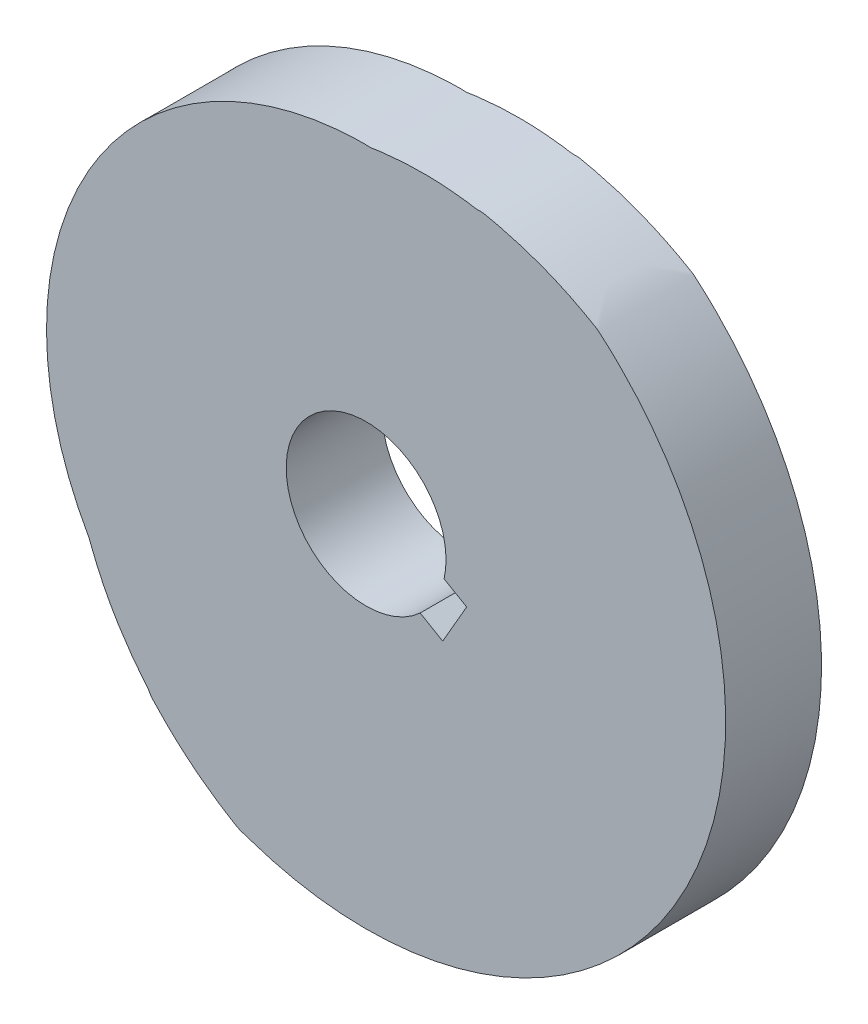
SolidWorks part; units mm, degrees
material "45"
ref_plane "前视基准面" through (0, 0, 0) normal (0, 0, 1) x (1, 0, 0)
ref_plane "上视基准面" through (0, 0, 0) normal (0, 1, 0) x (1, 0, 0)
ref_plane "右视基准面" through (0, 0, 0) normal (1, 0, 0) x (0, 0, -1)
ref_axis "基准轴1" through (0, 0, -88.99) along (0, 0, 1)
sketch "草图1" plane through (0, 0, 0) normal (0, 0, 1) x (1, 0, 0)
  arc A0 (28.9254, 34.472) -> (-15.3909, -42.2862) centre (0, 0) cw construction
  arc A1 (-34.641, -20) -> (0, 40) centre (0, 0) cw construction
  spline S0 degree 3 poles (0, 40) (0.4748, 39.9243) (1.1694, 40.08) (2.1071, 40.1955) (2.8169, 40.2793) (3.5303, 40.348) (4.247, 40.4047) (4.9668, 40.4484) (5.6893, 40.4794) (6.4145, 40.4974) (7.142, 40.5024) (7.8716, 40.4943) (8.6031, 40.473) (9.3363, 40.4385) (10.0709, 40.3908) (10.8066, 40.3293) (11.5433, 40.2558) (12.2803, 40.1639) (13.0194, 40.0767) (13.7627, 39.9054) (14.5314, 39.9845) (15.2755, 39.7844) (16.0159, 39.6423) (16.7537, 39.4678) (17.491, 39.2847) (18.2267, 39.0865) (18.9609, 38.8748) (19.6932, 38.6494) (20.4234, 38.4102) (21.1513, 38.1572) (21.8765, 37.8905) (22.5988, 37.6101) (23.318, 37.316) (24.0338, 37.0082) (24.7459, 36.6867) (25.4541, 36.3517) (26.1581, 36.003) (26.8577, 35.6409) (27.7855, 35.1393) (28.472, 34.744) (28.9254, 34.472) knots 0 0 0 0 0.046842 0.070536 0.094303 0.11814 0.142049 0.16603 0.190082 0.214205 0.2384 0.262667 0.287004 0.311414 0.335895 0.360447 0.385071 0.409766 0.434533 0.459372 0.485336 0.510389 0.535514 0.56071 0.585978 0.611317 0.636728 0.662211 0.687765 0.713391 0.739088 0.764857 0.790697 0.816609 0.842593 0.868649 0.894776 0.920974 0.947244 1 1 1 1 construction
  spline S1 degree 3 poles (-15.3909, -42.2862) (-15.9186, -42.1748) (-16.5847, -41.7396) (-17.4865, -41.1963) (-18.1511, -40.769) (-18.8073, -40.3331) (-19.4535, -39.8863) (-20.0899, -39.4294) (-20.7163, -38.9623) (-21.3325, -38.4855) (-21.9384, -37.9991) (-22.5339, -37.5033) (-23.1187, -36.9983) (-23.6928, -36.4844) (-24.256, -35.9616) (-24.8084, -35.4306) (-25.3487, -34.8905) (-25.8817, -34.3453) (-26.3883, -33.7811) (-26.9465, -33.2438) (-27.2781, -32.5412) (-27.8109, -31.9896) (-28.2696, -31.398) (-28.7312, -30.8107) (-29.1768, -30.214) (-29.6115, -29.612) (-30.0338, -29.0038) (-30.4441, -28.39) (-30.842, -27.7707) (-31.2276, -27.1462) (-31.6009, -26.5167) (-31.9617, -25.8825) (-32.31, -25.2438) (-32.6458, -24.6008) (-32.9691, -23.9538) (-33.2797, -23.3031) (-33.5777, -22.6488) (-33.863, -21.9913) (-34.226, -21.1118) (-34.48, -20.4461) (-34.641, -20) knots 0 0 0 0 0.05239 0.07866 0.104858 0.130984 0.15704 0.183024 0.208936 0.234777 0.260546 0.286245 0.311871 0.337427 0.362911 0.388323 0.413664 0.438934 0.464133 0.48926 0.51529 0.540203 0.565044 0.589814 0.614513 0.639141 0.663697 0.688182 0.712596 0.736938 0.761209 0.785409 0.809538 0.833595 0.857581 0.881495 0.905339 0.929111 0.952812 1 1 1 1 construction
  spline S2 degree 3 poles (29.1413, 34.2897) (78.7299, -7.8534) (46.2107, -64.2234) (-15.0958, -42.3924) (-15.1612, -42.3691) (-15.2919, -42.3222) (-15.4926, -42.2655) (-15.6255, -42.2248) (-15.6911, -42.2019) (-16.092, -42.0621) (-16.6727, -41.6866) (-17.4865, -41.1963) (-18.1511, -40.769) (-18.8073, -40.3331) (-19.4535, -39.8863) (-20.0899, -39.4294) (-20.7163, -38.9623) (-21.3325, -38.4855) (-21.9384, -37.9991) (-22.5339, -37.5033) (-23.1187, -36.9983) (-23.6928, -36.4844) (-24.256, -35.9616) (-24.8084, -35.4306) (-25.3487, -34.8905) (-25.8817, -34.3453) (-26.3883, -33.7811) (-26.9465, -33.2438) (-27.2781, -32.5412) (-27.8109, -31.9896) (-28.2696, -31.398) (-28.7312, -30.8107) (-29.1768, -30.214) (-29.6115, -29.612) (-30.0338, -29.0038) (-30.4441, -28.39) (-30.842, -27.7707) (-31.2276, -27.1462) (-31.6009, -26.5167) (-31.9617, -25.8825) (-32.31, -25.2438) (-32.6458, -24.6008) (-32.9691, -23.9538) (-33.2797, -23.3031) (-33.5777, -22.6488) (-33.863, -21.9913) (-34.1884, -21.203) (-34.4093, -20.6302) (-34.5395, -20.2779) (-34.5623, -20.2161) (-34.6077, -20.0925) (-34.6917, -19.9123) (-34.757, -19.7979) (-34.7894, -19.7407) (-51.6998, 10.0609) (-34.5699, 39.7368) (-0.3059, 39.9988) (-0.238, 39.9993) (-0.1022, 40) (0.101, 39.9831) (0.2367, 39.9751) (0.3045, 39.9739) (0.6733, 39.9673) (1.2696, 40.0924) (2.1071, 40.1955) (2.8169, 40.2793) (3.5303, 40.348) (4.247, 40.4047) (4.9668, 40.4484) (5.6893, 40.4794) (6.4145, 40.4974) (7.142, 40.5024) (7.8716, 40.4943) (8.6031, 40.473) (9.3363, 40.4385) (10.0709, 40.3908) (10.8066, 40.3293) (11.5433, 40.2558) (12.2803, 40.1639) (13.0194, 40.0767) (13.7627, 39.9054) (14.5314, 39.9845) (15.2755, 39.7844) (16.0159, 39.6423) (16.7537, 39.4678) (17.491, 39.2847) (18.2267, 39.0865) (18.9609, 38.8748) (19.6932, 38.6494) (20.4234, 38.4102) (21.1513, 38.1572) (21.8765, 37.8905) (22.5988, 37.6101) (23.318, 37.316) (24.0338, 37.0082) (24.7459, 36.6867) (25.4541, 36.3517) (26.1581, 36.003) (26.8577, 35.6409) (27.7042, 35.1832) (28.3117, 34.8359) (28.6873, 34.6138) (28.7407, 34.5823) (28.8472, 34.519) (28.9994, 34.4099) (29.0941, 34.3299) (29.1413, 34.2897) (78.7299, -7.8534) (46.2107, -64.2234) knots -0.000851 0 0 0 0.403816 0.403816 0.403816 0.404766 0.405716 0.406667 0.406667 0.406667 0.412478 0.416098 0.419709 0.42331 0.426901 0.430482 0.434054 0.437616 0.441167 0.444709 0.448241 0.451764 0.455276 0.458778 0.462271 0.465754 0.469227 0.47269 0.476278 0.479712 0.483136 0.48655 0.489954 0.493348 0.496733 0.500107 0.503472 0.506827 0.510173 0.513508 0.516834 0.520149 0.523455 0.526751 0.530038 0.533314 0.536581 0.541732 0.541732 0.541732 0.542635 0.543538 0.544441 0.544441 0.544441 0.859757 0.859757 0.859757 0.860688 0.861619 0.86255 0.86255 0.86255 0.867607 0.870867 0.874136 0.877415 0.880703 0.884002 0.88731 0.890629 0.893957 0.897295 0.900642 0.904 0.907367 0.910744 0.914132 0.917528 0.920935 0.924352 0.927923 0.931369 0.934825 0.938291 0.941767 0.945252 0.948747 0.952253 0.955768 0.959293 0.962827 0.966372 0.969926 0.973491 0.977065 0.980649 0.984242 0.987846 0.99146 0.997448 0.997448 0.997448 0.998299 0.999149 1 1 1 1.403816 1.403816 1.403816 weights 1 0.453445 0.453445 1 1 1 1 1 1 1 1 1 1 1 1 1 1 1 1 1 1 1 1 1 1 1 1 1 1 1 1 1 1 1 1 1 1 1 1 1 1 1 1 1 1 1 1 1 1 1 1 1 1 1 0.671021 0.671021 1 1 1 1 1 1 1 1 1 1 1 1 1 1 1 1 1 1 1 1 1 1 1 1 1 1 1 1 1 1 1 1 1 1 1 1 1 1 1 1 1 1 1 1 1 1 1 1 1 1 1 0.453445 0.453445 only from (29.1413, 34.2897) to (29.1413, 34.2897)
  point P0 (0, 0)
extrude "凸台-拉伸1" add sketch "草图1" along normal blind 12
sketch "草图2" plane through (0, 0, 0) normal (0, 0, 1) x (1, 0, 0)
  line L0 (9.7614, -2.1716) -> (12.5851, -3.8019)
  line L1 (12.5851, -3.8019) -> (9.5851, -8.9981)
  line L2 (9.5851, -8.9981) -> (6.7614, -7.3678)
  arc A0 (9.7614, -2.1716) -> (6.7614, -7.3678) centre (0, 0) ccw
extrude "切除-拉伸1" cut sketch "草图2" against normal blind 12 and the other way blind 12
